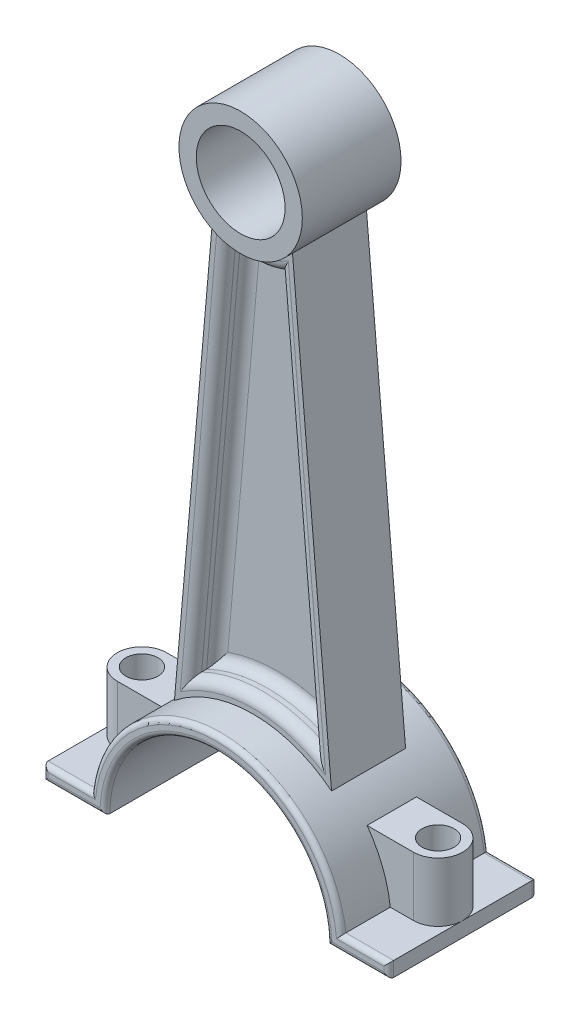
SolidWorks part; units mm, degrees
ref_plane "Front Plane" through (0, 0, 0) normal (0, 0, 1) x (1, 0, 0)
ref_plane "Top Plane" through (0, 0, 0) normal (0, 1, 0) x (1, 0, 0)
ref_plane "Right Plane" through (0, 0, 0) normal (1, 0, 0) x (0, 0, -1)
sketch "Sketch1" plane through (0, 0, 0) normal (0, 0, 1) x (1, 0, 0)
  line L0 (0, 0) -> (0, -120) construction
  line L1 (-35, -120) -> (-22.5, -120)
  line L2 (22.5, -120) -> (35, -120)
  line L3 (-8, -9.6047) -> (-15.9152, -100.0763)
  line L4 (8, -9.6047) -> (15.9152, -100.0763)
  line L5 (-35, -117) -> (-25.3229, -117)
  line L6 (25.3229, -117) -> (35, -117)
  line L7 (-35, -117) -> (-35, -120)
  line L8 (35, -117) -> (35, -120)
  circle A0 centre (0, 0) radius 9
  circle A1 centre (0, 0) radius 12.5
  arc A2 (22.5, -120) -> (-22.5, -120) centre (0, -120) ccw
  arc A3 (25.3229, -117) -> (-25.3229, -117) centre (0, -120) ccw
  point P9 (0, -120)
  dimension "D1" = 25
  dimension "D2" = 18
  dimension "D4" = 45
  dimension "D3" = 120
  dimension "D5" = 70
  dimension "D6" = 12.5
  dimension "D7" = 8
  dimension "D8" = 5
  dimension "D9" = 3
extrude "Boss-Extrude2" add sketch "Sketch1" along normal mid plane 20 contours A0 A1 region at (-5.1533, 10.9991, 0)
extrude "Boss-Extrude3" add sketch "Sketch1<8>" along normal mid plane 30 separate body contours A2 L1 L7 L5 A3 L6 L8 L2
sketch "Sketch1<8>" plane through (0, 0, 0) normal (0, 0, 1) x (1, 0, 0) same geometry as "Sketch1"
extrude "Boss-Extrude5" add sketch "Sketch1<10>" along normal mid plane 15 contours L0 A1 L3 A3 | A1 L0 A3 L4 region at (6.2546, -58.3141, 0) region at (-6.2546, -58.3141, 0)
sketch "Sketch1<10>" plane through (0, 0, 0) normal (0, 0, 1) x (1, 0, 0) same geometry as "Sketch1"
sketch "Sketch2" plane through (0, 0, 0) normal (0, 0, 1) x (1, 0, 0)
  line L2 (15.9152, -100.0763) -> (8, -9.6047)
  line L3 (-8, -9.6047) -> (-15.9152, -100.0763)
  line L4 (15.9152, -100.0763) -> (8, -9.6047)
  line L5 (-8, -9.6047) -> (-15.9152, -100.0763)
  line L8 (12.4019, -94.3399) -> (5.4187, -14.522)
  line L9 (-5.4187, -14.522) -> (-12.4019, -94.3399)
  line L10 (12.4019, -94.3399) -> (5.4187, -14.522)
  line L11 (-5.4187, -14.522) -> (-12.4019, -94.3399)
  arc A2 (15.9152, -100.0763) -> (-15.9152, -100.0763) centre (0, -120) ccw
  arc A3 (-8, -9.6047) -> (8, -9.6047) centre (0, 0) ccw
  arc A4 (15.9152, -100.0763) -> (-15.9152, -100.0763) centre (0, -120) ccw
  arc A5 (-8, -9.6047) -> (8, -9.6047) centre (0, 0) ccw
  arc A9 (12.4019, -94.3399) -> (-12.4019, -94.3399) centre (0, -120) ccw
  arc A10 (-5.4187, -14.522) -> (5.4187, -14.522) centre (0, 0) ccw
  arc A11 (12.4019, -94.3399) -> (-12.4019, -94.3399) centre (0, -120) ccw
  arc A12 (-5.4187, -14.522) -> (5.4187, -14.522) centre (0, 0) ccw
  dimension "D1" = 0
  dimension "D2" = 3
extrude "Cut-Extrude2" cut sketch "Sketch2" against normal blind 5 from offset 7.5 contours A11 L11 A12 L10
mirror "Mirror1" about plane through (0, 0, 0) normal (0, 0, 1) of "Cut-Extrude2"
sketch "Sketch3" plane through (0, -117, 0) normal (0, 1, 0) x (1, 0, 0)
  line L0 (-35, -15) -> (-35, 15) construction
  line L2 (-30, 5) -> (-30, -5)
  line L5 (-30, 5) -> (-18, 5)
  line L6 (-18, 5) -> (-18, -5)
  line L7 (-18, -5) -> (-30, -5)
  circle A0 centre (-30, 0) radius 5
  circle A1 centre (-30, 0) radius 3.25
  point P0 (-25, 0)
  line M8 (-25.3229, -15) -> (-25.3229, 15)
  dimension "D1" = 10
  dimension "D3" = 6.5
  dimension "D2" = 12
extrude "Boss-Extrude10" add sketch "Sketch3" against normal up to body from offset 12 contours A0 L7 M8 | A0 L5 M8 | A0 | L6 L7 L2 L5 region at (-26.4044, -117, -4.1253) region at (-26.4044, -117, 4.1253)
extrude "Cut-Extrude3" cut sketch "Sketch3<4>" against normal through all from surface contours L2 A1 | L2 A1 region at (-28.6207, -117, 0) region at (-31.3793, -117, 0) starting at face at (-26.5608, -105, 0)
sketch "Sketch3<4>" plane through (0, -117, 0) normal (0, 1, 0) x (1, 0, 0) same geometry as "Sketch3"
fillet "Fillet1" radius 2 16 edges at (0, -91.5, 2.5) (-8.9103, -54.4309, 2.5) (0, -15.5, 2.5) (8.9103, -54.4309, 2.5) (0, -15.5, -7.5) (0, -15.5, -2.5) (8.9103, -54.4309, -7.5) (8.9103, -54.4309, -2.5) (0, -91.5, -7.5) (0, -91.5, -2.5) (-8.9103, -54.4309, -7.5) (-8.9103, -54.4309, -2.5) (0, -15.5, 7.5) (0, -91.5, 7.5) (-8.9103, -54.4309, 7.5) (8.9103, -54.4309, 7.5)
mirror "Mirror2" about plane through (0, 0, 0) normal (1, 0, 0) of "Boss-Extrude10", "Cut-Extrude3"
fillet "Fillet2" radius 1 16 edges at (0, -97.5, 15) (-28.75, -120, 15) (-35, -118.5, 15) (-30.1615, -117, 15) (0, -94.5, 15) (30.1615, -117, 15) (35, -118.5, 15) (28.75, -120, 15) (35, -118.5, -15) (30.1615, -117, -15) (0, -94.5, -15) (-30.1615, -117, -15) (-35, -118.5, -15) (-28.75, -120, -15) (0, -97.5, -15) (28.75, -120, -15)
